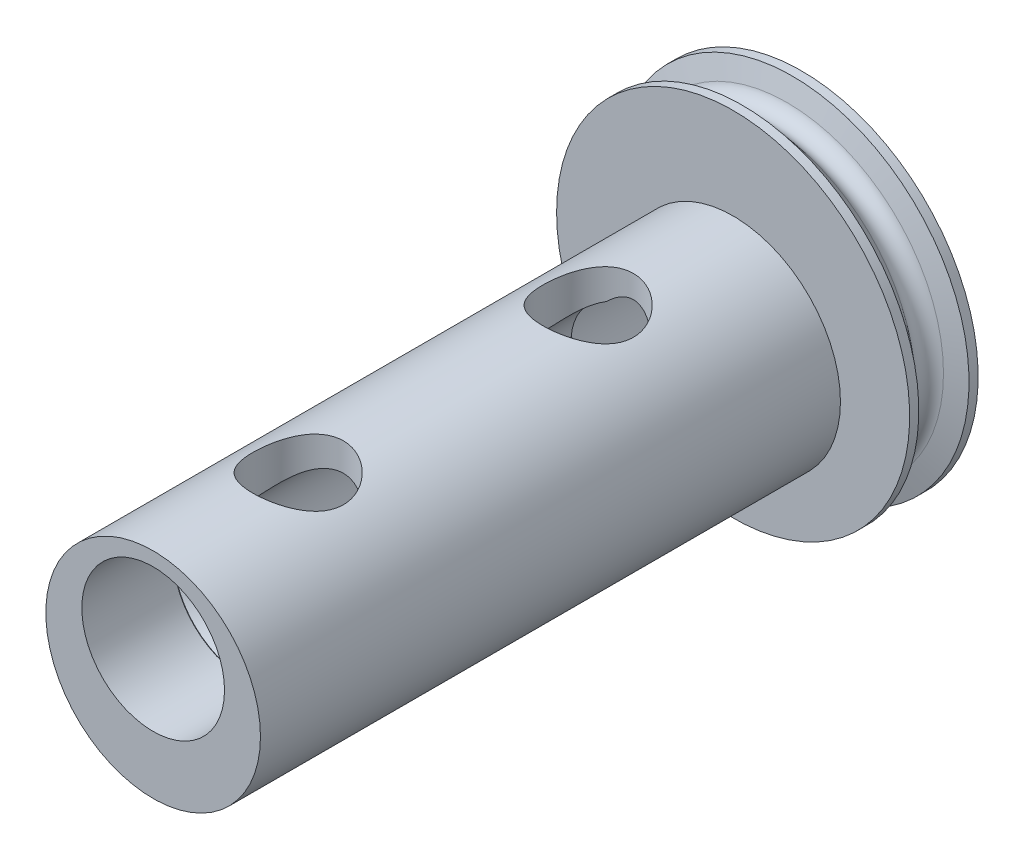
SolidWorks part; units mm, degrees
material "ABS"
ref_plane "Front Plane" through (0, 0, 0) normal (0, 0, 1) x (1, 0, 0)
ref_plane "Top Plane" through (0, 0, 0) normal (0, 1, 0) x (1, 0, 0)
ref_plane "Right Plane" through (0, 0, 0) normal (1, 0, 0) x (0, 0, -1)
sketch "Sketch1" plane through (0, 0, 0) normal (0, 0, 1) x (1, 0, 0)
  circle A0 centre (0, 1.938) radius 6.25
  circle A1 centre (0, 0) radius 9.525 construction
  circle A2 centre (0, 0) radius 9.525 construction
  circle A3 centre (0, 0) radius 9.4
  dimension "D1" = 12.5
  dimension "D3" = 0.125
  dimension "D2" = 1.938
extrude "Boss-Extrude1" add sketch "Sketch1" against normal up to surface (50.8 mm away)
ref_axis "Axis1" through (0, 1.938, -50.8) along (0, 0, 1)
sketch "Sketch3" plane through (0, 0, 0) normal (1, 0, 0) x (0, 0, -1)
  line L0 (50.8, 8.188) -> (50.8, 17.4)
  line L1 (50.8, 17.4) -> (51.6, 17.4)
  line L2 (51.6, 17.4) -> (53.4649, 15.1775)
  line L3 (55.527, 15.6347) -> (56, 17.4)
  line L4 (56, 17.4) -> (56.8, 17.4)
  line L5 (56.8, 17.4) -> (56.8, 9.246)
  line L6 (50.8, -9.4) -> (50.8, 9.4) construction
  line L9 (50.8, 9.4) -> (0, 9.4) construction
  line L10 (50.8, 8.188) -> (56.8, 9.246)
  line L11 (50.8, 8.188) -> (0, 8.188) construction
  arc A0 (53.4649, 15.1775) -> (55.527, 15.6347) centre (54.3769, 15.9429) ccw
  point P16 (25.4, 9.4)
  dimension "D1" = 50
  dimension "D3" = 1.1906
  dimension "D2" = 0.8
  dimension "D4" = 8
  dimension "D5" = 75
  dimension "D6" = 6
  dimension "D8" = 80
revolve "Revolve1" add sketch "Sketch3" angle 360 about axis through (0, 1.938, -50.8) along (0, 0, 1)
ref_plane "Plane1" through (0, 0, -28.4) normal (0, 0, 1) x (1, 0, 0)
ref_plane "Plane2" through (0, 0, -54.3769) normal (0, 0, 1) x (1, 0, 0)
ref_plane "Plane3" through (0, 0, -25.4) normal (0, 0, 1) x (1, 0, 0)
sketch "Sketch7" plane through (0, 0, -25.4) normal (0, 0, 1) x (1, 0, 0)
  circle A0 centre (0, 1.938) radius 5
  circle A1 centre (0, 1.938) radius 6.25
  circle A2 centre (0, 1.938) radius 6.25 construction
  dimension "D1" = 10
extrude "Boss-Extrude2" add sketch "Sketch7" along normal offset from surface 8 and the other way offset from surface 8 up to face at (6.25, 1.938, 0) other way up to face at (9.4, 0, -50.8)
chamfer "Chamfer1" distance 1.2 angle 45 2 edges at (5, 1.938, -42.8) (5, 1.938, -8)
sketch "Sketch8" plane through (0, 0, 0) normal (0, 1, 0) x (1, 0, 0)
  circle A0 centre (0, 38.1) radius 3.9688
  circle A1 centre (0, 12.7) radius 3.9688
  dimension "D1" = 7.9375
extrude "Cut-Extrude3" cut sketch "Sketch8" along normal blind 26
